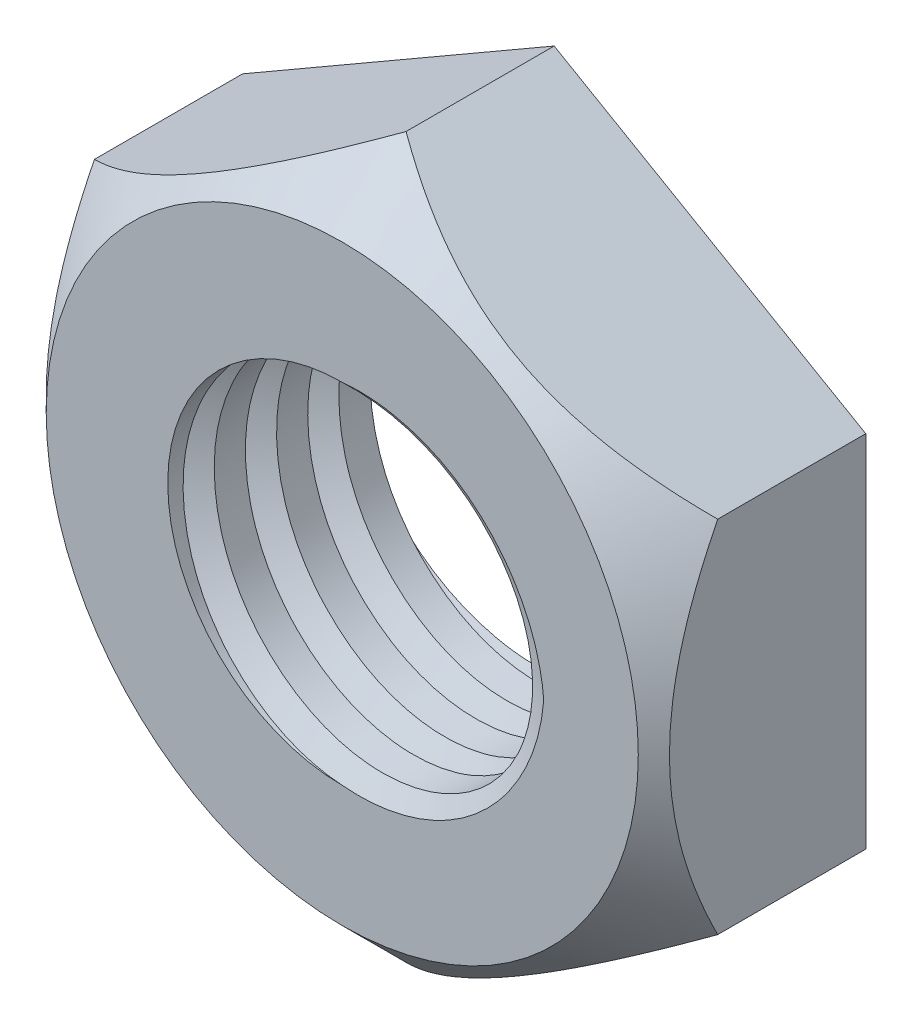
SolidWorks part; units mm, degrees
material "Galvanized Steel"
ref_plane "Front Plane" through (0, 0, 0) normal (0, 0, 1) x (1, 0, 0)
ref_plane "Top Plane" through (0, 0, 0) normal (0, 1, 0) x (1, 0, 0)
ref_plane "Right Plane" through (0, 0, 0) normal (1, 0, 0) x (0, 0, -1)
other "Configuration Table"
sketch "Sketch1" plane through (0, 0, 0) normal (0, 0, 1) x (1, 0, 0)
  line L0 (0, -55) -> (0, 55) construction
  line L1 (5, 2.8868) -> (0, 5.7735)
  line L2 (0, 5.7735) -> (-5, 2.8868)
  line L3 (-5, 2.8868) -> (-5, -2.8868)
  line L4 (-5, -2.8868) -> (0, -5.7735)
  line L5 (0, -5.7735) -> (5, -2.8868)
  line L6 (5, -2.8868) -> (5, 2.8868)
  circle A0 centre (0, 0) radius 5 construction
  circle A1 centre (0, 0) radius 2.8
extrude "Boss-Extrude1" add sketch "Sketch1" along normal blind 3.4
ref_axis "Axis1" through (0, 0, 3.4) along (0, 0, -1)
sketch "Sketch3" plane through (0, 0, 3.4) normal (0, 0, 1) x (1, 0, 0)
  circle A0 centre (0, 0) radius 2.8
curve "Helix/Spiral1" pitch 1 height 6 radius 2.8 centre (0, 0, 3.4) axis (0, 0, -1) start towards (1, 0, 0)
sketch "Sketch4" plane through (0, 0, 0) normal (0, 1, 0) x (1, 0, 0)
  line L0 (0, -3.575) -> (0, 3.575) construction
  line L1 (3.233, 2.6) -> (2.5835, 2.975)
  line L2 (2.5835, 2.975) -> (2.5835, 2.225)
  line L3 (2.5835, 2.225) -> (3.233, 2.6)
  circle A0 centre (2.8, 2.6) radius 0.2165 construction
  dimension "D1" = 2.6
  dimension "D2" = 2.8
sweep "Cut-Sweep2" cut profiles "Sketch4" path "Helix/Spiral1" align with end faces yes
sketch "Sketch8" plane through (0, 0, 3.4) normal (0, 0, 1) x (1, 0, 0)
  circle A0 centre (0, 0) radius 4.75
extrude "Cut-Extrude1" cut sketch "Sketch8" against normal blind 3.4 draft 45 flip side to cut
